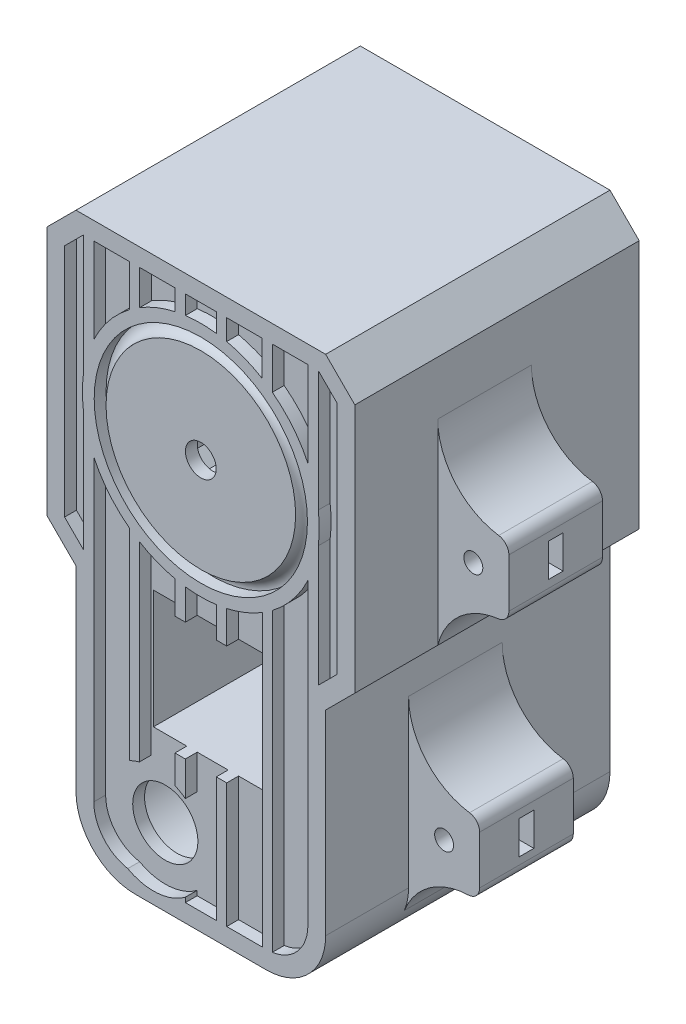
SolidWorks part; units mm, degrees
ref_plane "Alzado" through (0, 0, 0) normal (0, 0, 1) x (1, 0, 0)
ref_plane "Planta" through (0, 0, 0) normal (0, 1, 0) x (1, 0, 0)
ref_plane "Vista lateral" through (0, 0, 0) normal (1, 0, 0) x (0, 0, -1)
sketch "Croquis1" plane through (0, 0, 0) normal (0, 0, 1) x (1, 0, 0)
  line L0 (-19, -21) -> (-21, -19)
  line L1 (19, -21) -> (-19, -21)
  line L2 (21, -19) -> (21, 19)
  line L3 (19, 21) -> (-19, 21)
  line L4 (-21, -19) -> (-21, 19)
  line L5 (21, -21) -> (-21, 21) construction
  line L6 (21, 21) -> (-21, -21) construction
  line L7 (-19, 21) -> (-21, 19)
  line L8 (21, 19) -> (19, 21)
  line L9 (21, -19) -> (19, -21)
  line L10 (26, -21.0711) -> (26, 21.0711)
  line L11 (26, 21.0711) -> (21.0711, 26)
  line L12 (21.0711, 26) -> (-21.0711, 26)
  line L13 (-21.0711, 26) -> (-26, 21.0711)
  line L14 (-26, -21.0711) -> (-26, 21.0711)
  line L15 (-21.0711, -26) -> (-26, -21.0711)
  line L16 (21.0711, -26) -> (-21.0711, -26)
  line L17 (26, -21.0711) -> (21.0711, -26)
  point P0 (0, 0)
  dimension "D1" = 42
  dimension "D2" = 42
  dimension "D3" = 5
extrude "Saliente-Extruir1" add sketch "Croquis1" along normal mid plane 44
sketch "Croquis2" plane through (0, -26, 0) normal (0, -1, 0) x (1, 0, 0)
  line L4 (-21.0711, -22) -> (21.0711, -22)
  line L5 (21.0711, -22) -> (21.0711, 22)
  line L6 (21.0711, 22) -> (-21.0711, 22)
  line L7 (-21.0711, 22) -> (-21.0711, -22)
  line L8 (-21.0711, -22) -> (21.0711, -22)
  line L9 (21.0711, -22) -> (21.0711, 22)
  line L10 (21.0711, 22) -> (-21.0711, 22)
  line L11 (-21.0711, 22) -> (-21.0711, -22)
  dimension "D1" = 0
extrude "Saliente-Extruir2" add sketch "Croquis2" along normal blind 8
sketch "Croquis3" plane through (0, 0, 0) normal (0, 0, 1) x (1, 0, 0)
  line L0 (-19, -21) -> (19, -21) construction
  line L1 (-16.8806, -21) -> (16.8806, -21)
  line L2 (-16.8806, -21) -> (-16.8806, -29)
  line L3 (-16.8806, -29) -> (16.8806, -29)
  line L4 (16.8806, -21) -> (16.8806, -29)
  line L5 (0, 18.4155) -> (0, -35.026) construction
  dimension "D1" = 33.7612
  dimension "D2" = 8
extrude "Cortar-Extruir1" cut sketch "Croquis3" against normal through all contours L2 L1 L4 L3
sketch "Croquis4" plane through (0, 0, 22) normal (0, 0, -1) x (-1, 0, 0)
  line L10 (-26, -21.0711) -> (-21.0711, -26)
  line L11 (-21.0711, -26) -> (-21.0711, -34)
  line L12 (-21.0711, -34) -> (21.0711, -34)
  line L13 (21.0711, -34) -> (21.0711, -26)
  line L14 (21.0711, -26) -> (26, -21.0711)
  line L15 (26, -21.0711) -> (26, 21.0711)
  line L16 (26, 21.0711) -> (21.0711, 26)
  line L17 (21.0711, 26) -> (-21.0711, 26)
  line L18 (-21.0711, 26) -> (-26, 21.0711)
  line L19 (-26, 21.0711) -> (-26, -21.0711)
  line L20 (-26, -21.0711) -> (-21.0711, -26)
  line L21 (-21.0711, -26) -> (-21.0711, -34)
  line L22 (-21.0711, -34) -> (21.0711, -34)
  line L23 (21.0711, -34) -> (21.0711, -26)
  line L24 (21.0711, -26) -> (26, -21.0711)
  line L25 (26, -21.0711) -> (26, 21.0711)
  line L26 (26, 21.0711) -> (21.0711, 26)
  line L27 (21.0711, 26) -> (-21.0711, 26)
  line L28 (-21.0711, 26) -> (-26, 21.0711)
  line L29 (-26, 21.0711) -> (-26, -21.0711)
  circle A0 centre (0, 0) radius 11
  dimension "D2" = 22
  dimension "D1" = 0
extrude "Saliente-Extruir4" add sketch "Croquis4" against normal blind 2
sketch "Croquis7" plane through (0, 0, 24) normal (0, 0, 1) x (1, 0, 0)
  circle A0 centre (0, 0) radius 2.6
  circle A3 centre (0, 0) radius 16
  circle A4 centre (0, 0) radius 16
  dimension "D2" = 5.2
  dimension "D1" = 5
extrude "Saliente-Extruir5" add sketch "Croquis7" along normal blind 2
sketch "Croquis6" plane through (0, -29, 0) normal (0, 1, 0) x (1, 0, 0)
  line L0 (0, -24.5904) -> (0, 23.7869) construction
  line L1 (-14, 18) -> (14, 18)
  line L2 (-14, 18) -> (-14, 6)
  line L3 (-14, 6) -> (14, 6)
  line L4 (14, 18) -> (14, 6)
  dimension "D1" = 28
  dimension "D2" = 12
  dimension "D3" = 18
extrude "Cortar-Extruir3" cut sketch "Croquis6" against normal blind 13
sketch "Croquis8" plane through (0, 0, 0) normal (0, 0, 1) x (1, 0, 0)
  line L0 (-26, -21.0711) -> (-26, 21.0711)
  line L1 (-26, -21.0711) -> (-26, 21.0711)
  line L2 (-26, 21.0711) -> (-21.0711, 26)
  line L3 (-26, 21.0711) -> (-21.0711, 26)
  line L4 (-21.0711, 26) -> (21.0711, 26)
  line L5 (-21.0711, 26) -> (21.0711, 26)
  line L6 (21.0711, 26) -> (26, 21.0711)
  line L7 (21.0711, 26) -> (26, 21.0711)
  line L8 (26, 21.0711) -> (26, -21.0711)
  line L9 (26, 21.0711) -> (26, -21.0711)
  line L10 (26, -21.0711) -> (21.0711, -26)
  line L11 (26, -21.0711) -> (21.0711, -26)
  line L12 (21.0711, -26) -> (21.0711, -34)
  line L13 (21.0711, -26) -> (21.0711, -34)
  line L14 (21.0711, -34) -> (-21.0711, -34)
  line L15 (21.0711, -34) -> (-21.0711, -34)
  line L16 (-21.0711, -34) -> (-21.0711, -26)
  line L17 (-21.0711, -34) -> (-21.0711, -26)
  line L18 (-21.0711, -26) -> (-26, -21.0711)
  line L19 (-21.0711, -26) -> (-26, -21.0711)
  line L20 (0, 0) -> (-39.949, 0) construction
  line L21 (0, 0) -> (0, 31.7363) construction
  line L22 (26, -12) -> (38, -12)
  line L23 (-26, 0) -> (-38, 0)
  line L24 (-26, 0) -> (-26, -12)
  line L25 (-26, -12) -> (-38, -12)
  line L26 (-38, 0) -> (-38, -12)
  line L27 (38, 0) -> (38, -12)
  line L28 (26, 0) -> (38, 0)
  line L29 (26, 0) -> (26, -12)
  line L30 (-38, -12) -> (-26, 0) construction
  circle A0 centre (-32, -6) radius 1.6
  circle A1 centre (32, -6) radius 1.6
  dimension "D3" = 3.2
  dimension "D1" = 12
  dimension "D2" = 12
extrude "Saliente-Extruir6" add sketch "Croquis8" along normal blind 12 and the other way blind 3.8 contours L23 L26 L25 L1 | L28 L9 L22 L27 region at (-32, -11.8303, 0) region at (26.1697, -6, 0)
sketch "Croquis9" plane through (38, 0, 0) normal (1, 0, 0) x (0, 0, -1)
  line L0 (3.8, -6) -> (-12, -6) construction
  line L1 (3.8, 0) -> (3.8, -12) construction
  line L2 (-12, 0) -> (-12, -12) construction
  line L4 (-2.85, -3.2) -> (-5.35, -3.2)
  line L5 (-2.85, -3.2) -> (-2.85, -8.8)
  line L6 (-2.85, -8.8) -> (-5.35, -8.8)
  line L7 (-5.35, -3.2) -> (-5.35, -8.8)
  line L8 (-2.85, -3.2) -> (-5.35, -8.8) construction
  line L9 (-2.85, -8.8) -> (-5.35, -3.2) construction
  point P6 (-4.1, -6)
  dimension "D1" = 5.6
  dimension "D2" = 2.5
extrude "Cortar-Extruir4" cut sketch "Croquis9" against normal blind 10
mirror "Simetría1" about plane through (0, 0, 0) normal (1, 0, 0) of "Cortar-Extruir4"
sketch "Croquis11" plane through (0, -34, 0) normal (0, -1, 0) x (1, 0, 0)
  line L4 (-21.0711, 24) -> (-21.0711, -22)
  line L5 (-21.0711, -22) -> (21.0711, -22)
  line L6 (21.0711, -22) -> (21.0711, 24)
  line L7 (21.0711, 24) -> (-21.0711, 24)
  line L8 (-21.0711, 24) -> (-21.0711, -22)
  line L9 (-21.0711, -22) -> (21.0711, -22)
  line L10 (21.0711, -22) -> (21.0711, 24)
  line L11 (21.0711, 24) -> (-21.0711, 24)
  dimension "D1" = 0
extrude "Saliente-Extruir8" add sketch "Croquis11" along normal blind 35
sketch "Croquis12" plane through (0, 0, -22) normal (0, 0, -1) x (-1, 0, 0)
  line L0 (0, 0) -> (0, -75.996) construction
  line L1 (18.0711, -66) -> (-18.0711, -66)
  line L2 (18.0711, -66) -> (18.0711, -38)
  line L3 (18.0711, -38) -> (-18.0711, -38)
  line L4 (-18.0711, -66) -> (-18.0711, -38)
  line L5 (21.0711, -69) -> (21.0711, -26) construction
  line L6 (21.0711, -69) -> (-21.0711, -69) construction
  dimension "D1" = 3
  dimension "D2" = 3
  dimension "D3" = 28
extrude "Cortar-Extruir5" cut sketch "Croquis12" against normal offset from surface (44 mm away) 2 up to face at (-16, 0, 24)
sketch "Croquis14" plane through (0, 0, 24) normal (0, 0, 1) x (1, 0, 0)
  line L0 (0, 0) -> (0, -70.2297) construction
  line L1 (10, -25) -> (-10, -25)
  line L2 (10, -25) -> (10, -45)
  line L3 (10, -45) -> (-10, -45)
  line L4 (-10, -25) -> (-10, -45)
  line L5 (10, -25) -> (-10, -45) construction
  line L6 (10, -45) -> (-10, -25) construction
  point P0 (0, -35)
  dimension "D1" = 35
  dimension "D2" = 20
  dimension "D3" = 20
extrude "Cortar-Extruir7" cut sketch "Croquis14" against normal blind 25
sketch "Croquis15" plane through (0, 0, 22) normal (0, 0, -1) x (-1, 0, 0)
  line L0 (-10, -38) -> (-18.0711, -38)
  line L1 (-18.0711, -38) -> (-18.0711, -49)
  line L2 (-18.0711, -49) -> (18.0711, -49)
  line L3 (18.0711, -49) -> (18.0711, -38)
  line L4 (18.0711, -38) -> (10, -38)
  line L5 (10, -38) -> (10, -45)
  line L6 (10, -45) -> (-10, -45)
  line L7 (-10, -45) -> (-10, -38)
  dimension "D1" = 4
  dimension "D2" = 90
  dimension "D3" = 90
extrude "Saliente-Extruir9" add sketch "Croquis15" along normal blind 25
sketch "Croquis16" plane through (0, 0, -3) normal (0, 0, -1) x (-1, 0, 0)
  line L1 (-10, -45) -> (10, -45)
  line L2 (-10, -45) -> (-10, -25)
  line L3 (-10, -25) -> (10, -25)
  line L4 (10, -45) -> (10, -25)
extrude "Saliente-Extruir11" add sketch "Croquis16" against normal blind 3.2
sketch "Croquis17" plane through (0, -49, 0) normal (0, -1, 0) x (1, 0, 0)
  line L0 (0, -10) -> (0, 26) construction
  line L1 (16, 26) -> (-16, 26) construction
  circle A0 centre (0, 8) radius 1.6
  point P6 (0, 0)
  dimension "D1" = 3.2
  dimension "D2" = 8
extrude "Cortar-Extruir8" cut sketch "Croquis17" against normal blind 40
sketch "Croquis18" plane through (0, -21, 0) normal (0, 1, 0) x (1, 0, 0)
  circle A0 centre (0, -8) radius 1.6 construction
  circle A1 centre (0, -8) radius 1.6
  circle A2 centre (0, -8) radius 4.8
  dimension "D1" = 3.2
extrude "Cortar-Extruir9" cut sketch "Croquis18" against normal blind 2
sketch "Croquis13" plane through (0, 0, 22) normal (0, 0, -1) x (-1, 0, 0)
  line L0 (18.0711, -52) -> (-18.0711, -52) construction
  line L1 (18.0711, -66) -> (18.0711, -38) construction
  line L2 (-18.0711, -38) -> (-18.0711, -66) construction
  line L3 (0, 0) -> (0, -68.0761) construction
  circle A0 centre (8, -58) radius 5.5
  point P8 (0, 0)
  point P9 (-8.0054, -58.5)
  point P13 (10.141, -58.5)
  dimension "D1" = 11
  dimension "D3" = 11
  dimension "D2" = 6
  dimension "D4" = 8
extrude "Cortar-Extruir6" cut sketch "Croquis13" against normal blind 2
fillet "Redondeo1" radius 10 2 edges at (-18.0711, -66, 0) (18.0711, -66, 0)
fillet "Redondeo2" radius 10 2 edges at (-21.0711, -69, 1) (21.0711, -69, 1)
sketch "Croquis19" plane through (21.0711, 0, 0) normal (1, 0, 0) x (0, 0, -1)
  line L0 (0, 0) -> (0, -69) construction
  line L1 (22, -69) -> (-24, -69) construction
  line L2 (3.8, 0) -> (3.8, -12) construction
  line L3 (3.8, -55) -> (-12, -55)
  line L4 (3.8, -55) -> (3.8, -43)
  line L5 (3.8, -43) -> (-12, -43)
  line L6 (-12, -55) -> (-12, -43)
  line L7 (-12, 0) -> (-12, -12) construction
  line L8 (-2.85, -8.8) -> (-2.85, -3.2) construction
  line L9 (-2.85, -51.8) -> (-5.35, -51.8)
  line L10 (-2.85, -51.8) -> (-2.85, -46.2)
  line L11 (-2.85, -46.2) -> (-5.35, -46.2)
  line L12 (-5.35, -51.8) -> (-5.35, -46.2)
  line L13 (-5.35, -3.2) -> (-5.35, -8.8) construction
  line L14 (3.8, -49) -> (-12, -49) construction
  dimension "D1" = 12
  dimension "D2" = 43
  dimension "D3" = 5.6
extrude "Saliente-Extruir12" add sketch "Croquis19" along normal blind 12
sketch "Croquis20" plane through (0, 0, -3.8) normal (0, 0, -1) x (-1, 0, 0)
  line L0 (-33.0711, -49) -> (-21.0711, -49) construction
  line L1 (-33.0711, -55) -> (-33.0711, -43) construction
  line L2 (-21.0711, -59) -> (-21.0711, -26) construction
  line L3 (-27.0711, -55) -> (-27.0711, -43) construction
  line L4 (-33.0711, -55) -> (-21.0711, -55) construction
  line L5 (-33.0711, -43) -> (-21.0711, -43) construction
  circle A0 centre (-27.0711, -49) radius 1.6
  dimension "D1" = 3.2
extrude "Cortar-Extruir10" cut sketch "Croquis20" against normal through all
mirror "Simetría2" about plane through (0, 0, 0) normal (1, 0, 0) of "Saliente-Extruir12", "Cortar-Extruir10"
fillet "Redondeo3" radius 12 4 edges at (21.0711, -55, 4.1) (26, -12, 4.1) (26, 0, 4.1) (21.0711, -43, 4.1)
fillet "Redondeo4" radius 2 4 edges at (33.0711, -55, 4.1) (33.0711, -43, 4.1) (38, -12, 4.1) (38, 0, 4.1)
fillet "Redondeo5" radius 10 4 edges at (-21.0711, -55, 4.1) (-21.0711, -43, 4.1) (-26, -12, 4.1) (-26, 0, 4.1)
fillet "Redondeo6" radius 2 4 edges at (-33.0711, -43, 4.1) (-38, 0, 4.1) (-38, -12, 4.1) (-33.0711, -55, 4.1)
fillet "Redondeo7" radius 2 1 edges at (-16, 0, 24)
sketch "Croquis22" plane through (0, 0, 24) normal (0, 0, 1) x (1, 0, 0)
  line L20 (-18.0711, -24.7574) -> (-18.0711, -59)
  line L21 (-11.0711, -66) -> (11.0711, -66)
  line L22 (18.0711, -59) -> (18.0711, -24.7574)
  line L23 (18.0711, -24.7574) -> (23, -19.8284)
  line L24 (23, -19.8284) -> (23, 19.8284)
  line L25 (23, 19.8284) -> (19.8284, 23)
  line L26 (19.8284, 23) -> (-19.8284, 23)
  line L27 (-19.8284, 23) -> (-23, 19.8284)
  line L28 (-23, 19.8284) -> (-23, -19.8284)
  line L29 (-23, -19.8284) -> (-18.0711, -24.7574)
  line L30 (-18.0711, -24.7574) -> (-18.0711, -59)
  line L31 (-11.0711, -66) -> (11.0711, -66)
  line L32 (18.0711, -59) -> (18.0711, -24.7574)
  line L33 (18.0711, -24.7574) -> (23, -19.8284)
  line L34 (23, -19.8284) -> (23, 19.8284)
  line L35 (23, 19.8284) -> (19.8284, 23)
  line L36 (19.8284, 23) -> (-19.8284, 23)
  line L37 (-19.8284, 23) -> (-23, 19.8284)
  line L38 (-23, 19.8284) -> (-23, -19.8284)
  line L39 (-23, -19.8284) -> (-18.0711, -24.7574)
  line L40 (-21.0711, -26) -> (-21.0711, -59)
  line L41 (-11.0711, -69) -> (11.0711, -69)
  line L42 (21.0711, -59) -> (21.0711, -26)
  line L43 (21.0711, -26) -> (26, -21.0711)
  line L44 (26, -21.0711) -> (26, 21.0711)
  line L45 (26, 21.0711) -> (21.0711, 26)
  line L46 (21.0711, 26) -> (-21.0711, 26)
  line L47 (-21.0711, 26) -> (-26, 21.0711)
  line L48 (-26, 21.0711) -> (-26, -21.0711)
  line L49 (-26, -21.0711) -> (-21.0711, -26)
  line L50 (-21.0711, -26) -> (-21.0711, -59)
  line L51 (-11.0711, -69) -> (11.0711, -69)
  line L52 (21.0711, -59) -> (21.0711, -26)
  line L53 (21.0711, -26) -> (26, -21.0711)
  line L54 (26, -21.0711) -> (26, 21.0711)
  line L55 (26, 21.0711) -> (21.0711, 26)
  line L56 (21.0711, 26) -> (-21.0711, 26)
  line L57 (-21.0711, 26) -> (-26, 21.0711)
  line L58 (-26, 21.0711) -> (-26, -21.0711)
  line L59 (-26, -21.0711) -> (-21.0711, -26)
  circle A3 centre (0, 0) radius 18 construction
  arc A4 (-18.0711, -59) -> (-11.0711, -66) centre (-11.0711, -59) ccw
  arc A5 (11.0711, -66) -> (18.0711, -59) centre (11.0711, -59) ccw
  arc A6 (-18.0711, -59) -> (-11.0711, -66) centre (-11.0711, -59) ccw
  arc A7 (11.0711, -66) -> (18.0711, -59) centre (11.0711, -59) ccw
  arc A8 (-21.0711, -59) -> (-11.0711, -69) centre (-11.0711, -59) ccw
  arc A9 (11.0711, -69) -> (21.0711, -59) centre (11.0711, -59) ccw
  arc A10 (-21.0711, -59) -> (-11.0711, -69) centre (-11.0711, -59) ccw
  arc A11 (11.0711, -69) -> (21.0711, -59) centre (11.0711, -59) ccw
  circle A12 centre (0, 0) radius 20
  circle A13 centre (0, 0) radius 20
  circle A14 centre (0, 0) radius 18
  circle M26 centre (0, 0) radius 18
  line M32 (-21.0711, -26) -> (-21.0711, -59)
  arc M33 (-21.0711, -59) -> (-11.0711, -69) centre (-11.0711, -59) ccw
  line M34 (-11.0711, -69) -> (11.0711, -69)
  arc M35 (11.0711, -69) -> (21.0711, -59) centre (11.0711, -59) ccw
  line M36 (21.0711, -59) -> (21.0711, -26)
  line M37 (21.0711, -26) -> (26, -21.0711)
  line M38 (26, -21.0711) -> (26, 21.0711)
  line M39 (26, 21.0711) -> (21.0711, 26)
  line M40 (21.0711, 26) -> (-21.0711, 26)
  line M41 (-21.0711, 26) -> (-26, 21.0711)
  line M42 (-26, 21.0711) -> (-26, -21.0711)
  line M43 (-26, -21.0711) -> (-21.0711, -26)
  dimension "D1" = 3
  dimension "D2" = 0
  dimension "D3" = 2
extrude "Saliente-Extruir13" add sketch "Croquis22" along direction (0, 0, 1) on the side of the normal blind 2 contours A7 L31 A6 L30 L39 L38 L37 L36 L35 L34 L33 L32 M43 M32 M33 M34 M35 M36 M37 M38 M39 M40 M41 M42 | A13 M26 region at (-22.7697, -22.7697, 24) region at (-19.4343, 0, 24)
sketch "Croquis24" plane through (0, 0, 24) normal (0, 0, 1) x (1, 0, 0)
  line L0 (19.8284, 23) -> (19.8284, 2.6141)
  line L1 (18.0711, -24.7574) -> (23, -19.8284) construction
  line L2 (18.0711, -24.7574) -> (18.0711, -8.5695)
  line L3 (18.0711, 8.5695) -> (18.0711, 23)
  line L4 (12.0711, 23) -> (12.0711, 15.9465)
  line L5 (12.0711, -15.9465) -> (12.0711, -65.9282)
  line L6 (10.3111, 23) -> (10.3111, 17.1371)
  line L7 (10, -45) -> (10, -25)
  line L8 (10, -25) -> (-10, -25)
  line L9 (-10, -25) -> (-10, -45)
  line L10 (-10, -45) -> (10, -45)
  line L11 (10, -45) -> (10, -25)
  line L12 (10, -25) -> (-10, -25)
  line L13 (-11.0711, -66) -> (11.0711, -66)
  line L14 (18.0711, -59) -> (18.0711, -24.7574)
  line L15 (18.0711, -24.7574) -> (23, -19.8284)
  line L16 (23, -19.8284) -> (23, 19.8284)
  line L17 (23, 19.8284) -> (19.8284, 23)
  line L18 (19.8284, 23) -> (-19.8284, 23)
  line L19 (-19.8284, 23) -> (-23, 19.8284)
  line L20 (-23, 19.8284) -> (-23, -19.8284)
  line L21 (-23, -19.8284) -> (-18.0711, -24.7574)
  line L22 (-18.0711, -24.7574) -> (-18.0711, -59)
  line L23 (-11.0711, -66) -> (11.0711, -66)
  line L24 (18.0711, -59) -> (18.0711, -24.7574)
  line L25 (18.0711, -24.7574) -> (23, -19.8284)
  line L26 (23, -19.8284) -> (23, 19.8284)
  line L27 (23, 19.8284) -> (19.8284, 23)
  line L28 (19.8284, 23) -> (-19.8284, 23)
  line L29 (-19.8284, 23) -> (-23, 19.8284)
  line L30 (-23, 19.8284) -> (-23, -19.8284)
  line L31 (-23, -19.8284) -> (-18.0711, -24.7574)
  line L32 (-18.0711, -24.7574) -> (-18.0711, -59)
  line L33 (-10, -25) -> (-10, -45)
  line L34 (-10, -45) -> (10, -45)
  line L35 (10.3711, -66) -> (10.3711, -17.1009)
  line L36 (4.3711, -19.5165) -> (4.3711, -25)
  line L37 (4.3711, 23) -> (4.3711, 19.5165)
  line L38 (2.6111, 23) -> (2.6111, 19.8288)
  line L39 (10.3111, 15.9465) -> (10.3111, -65.9282) construction
  line L40 (2.6111, -19.8288) -> (2.6111, -25)
  line L41 (2.6111, -45) -> (2.6111, -66)
  line L42 (4.3711, -45) -> (4.3711, -66)
  line L43 (19.8284, -2.6141) -> (19.8284, -23)
  line L45 (12.0711, 15.9465) -> (12.0711, -65.9282) construction
  line L46 (10.3111, 23) -> (10.3111, 15.9465) construction
  circle A0 centre (0, 0) radius 20 construction
  circle A1 centre (0, 0) radius 20
  circle A2 centre (0, 0) radius 2.6 construction
  circle A3 centre (0, 0) radius 2.6
  arc A4 (11.0711, -66) -> (18.0711, -59) centre (11.0711, -59) ccw
  arc A5 (-18.0711, -59) -> (-11.0711, -66) centre (-11.0711, -59) ccw
  arc A6 (11.0711, -66) -> (18.0711, -59) centre (11.0711, -59) ccw
  arc A7 (-18.0711, -59) -> (-11.0711, -66) centre (-11.0711, -59) ccw
  point P43 (0, 0)
  circle M26 centre (0, 0) radius 20
  arc M28 (11.0711, -66) -> (18.0711, -59) centre (11.0711, -59) ccw
  line M30 (18.0711, -24.7574) -> (23, -19.8284)
  line M33 (19.8284, 23) -> (-19.8284, 23)
  dimension "D3" = 1.7574
  dimension "D4" = 6
  dimension "D7" = 1.7
  dimension "D8" = 1.76
  dimension "D9" = 6
  dimension "D1" = 0
  dimension "D2" = 0
  dimension "D5" = 1.76
  dimension "D6" = 2
extrude "Saliente-Extruir15" add sketch "Croquis24" along normal blind 2 contours L3 L0 M26 M33 | L43 L2 M26 M30 | L6 L4 M33 M26 | L28 L38 L37 M26 | L40 L12 L36 M26 | L35 L23 L5 M28 M26 | L42 L34 L41 L23 region at (18.9984, 14.5028, 24) region at (11.2182, 19.7731, 24) region at (18.9814, -14.9533, 24) region at (3.5049, 21.3419, 24) region at (11.2242, -41.2643, 24) region at (3.4997, -22.3423, 24) region at (3.4911, -55.5, 24)
mirror "Simetría9" about plane through (0, 0, 0) normal (1, 0, 0) of "Saliente-Extruir15"
sketch "Croquis25" plane through (0, 0, 26) normal (0, 0, 1) x (1, 0, 0)
  circle A0 centre (-8, -58) radius 9
  dimension "D1" = 18
extrude "Cortar-Extruir11" cut sketch "Croquis25" against normal up to surface (2 mm away) up to face at (-14.5986, -44.4874, 24)
